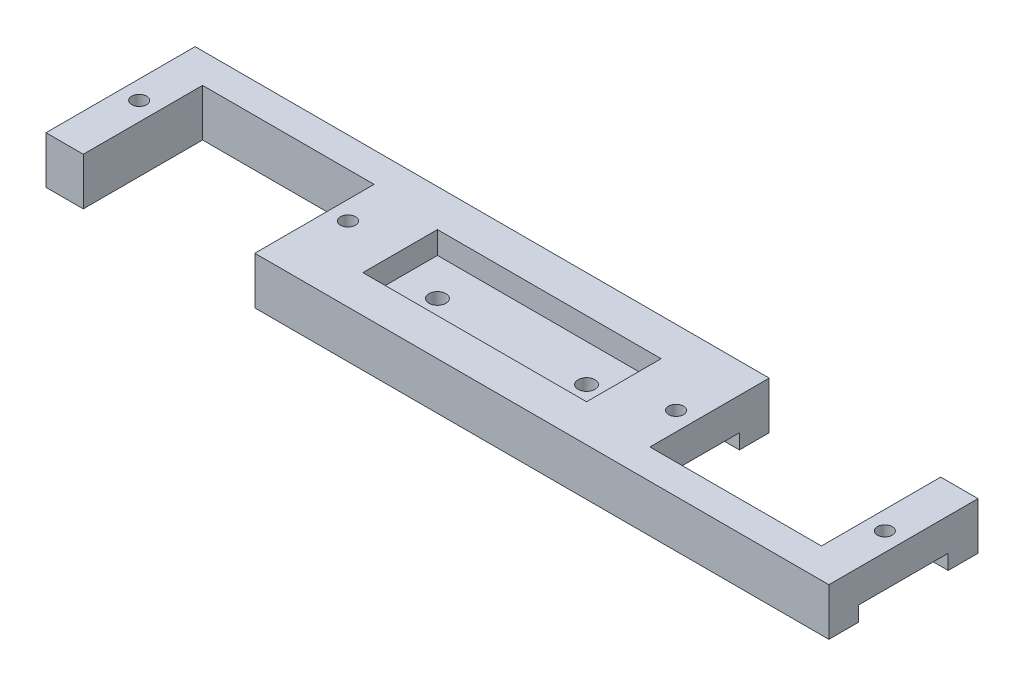
SolidWorks part; units mm, degrees
material "ABS"
ref_plane "Front" through (0, 0, 0) normal (0, 0, 1) x (1, 0, 0)
ref_plane "Top" through (0, 0, 0) normal (0, 1, 0) x (1, 0, 0)
ref_plane "Right" through (0, 0, 0) normal (1, 0, 0) x (0, 0, -1)
sketch "Sketch1" plane through (0, 0, 0) normal (0, 1, 0) x (1, 0, 0)
  line L1 (-52.5, 10) -> (52.5, 10)
  line L2 (-52.5, 10) -> (-52.5, -10)
  line L3 (-52.5, -10) -> (52.5, -10)
  line L4 (52.5, 10) -> (52.5, -10)
  line L5 (-52.5, 10) -> (52.5, -10) construction
  line L6 (-52.5, -10) -> (52.5, 10) construction
  point P0 (0, 0)
  dimension "D1" = 105
  dimension "D2" = 20
extrude "Boss-Extrude1" add sketch "Sketch1" along normal blind 6.35
sketch "Sketch3" plane through (0, 6.35, 0) normal (0, 1, 0) x (1, 0, 0)
  line L0 (-52.5, -10) -> (52.5, -10) construction
  line L1 (-47.5, -10) -> (-24.5, -10)
  line L2 (-47.5, -10) -> (-47.5, 6)
  line L3 (-47.5, 6) -> (-24.5, 6)
  line L4 (-24.5, -10) -> (-24.5, 6)
  line L5 (-52.5, 10) -> (-52.5, -10) construction
  line L6 (52.5, 10) -> (-52.5, 10) construction
  line L7 (52.5, -10) -> (52.5, 10) construction
  line L8 (24.5, 10) -> (47.5, 10)
  line L9 (24.5, 10) -> (24.5, -6)
  line L10 (24.5, -6) -> (47.5, -6)
  line L11 (47.5, 10) -> (47.5, -6)
  dimension "D1" = 23
  dimension "D2" = 5
  dimension "D3" = 4
  dimension "D4" = 5
  dimension "D5" = 4
extrude "Cut-Extrude1" cut sketch "Sketch3" against normal through all
sketch "Sketch4" plane through (0, 0, 0) normal (0, -1, 0) x (1, 0, 0)
  line L0 (24.5, -10) -> (24.5, 6) construction
  line L1 (24.5, 6) -> (19.5, 6)
  line L2 (24.5, 6) -> (24.5, -6)
  line L3 (24.5, -6) -> (19.5, -6)
  line L4 (19.5, 6) -> (19.5, -6)
  line L5 (47.5, 6) -> (47.5, -10) construction
  line L6 (47.5, 6) -> (52.5, 6)
  line L7 (47.5, 6) -> (47.5, -6)
  line L8 (47.5, -6) -> (52.5, -6)
  line L9 (52.5, 6) -> (52.5, -6)
  line L10 (24.5, -10) -> (52.5, 10) construction
  line L11 (24.5, 0) -> (47.5, 0) construction
  point P18 (38.5, 0)
  dimension "D1" = 5
  dimension "D2" = 12
extrude "Cut-Extrude2" cut sketch "Sketch4" against normal blind 2
hole_wizard "M2 Clearance Hole1" positions "Sketch7" profile "Sketch8" hole size "M2" standard "ANSI Metric" end condition through all
sketch "Sketch7" plane through (0, 6.35, 0) normal (0, 1, 0) x (1, 0, 0)
  line L0 (-52.5, 0) -> (52.5, 0) construction
  line L1 (-52.5, 10) -> (-52.5, -10) construction
  line L2 (52.5, -10) -> (52.5, 10) construction
  line L3 (24.5, 10) -> (24.5, -6) construction
  line L4 (47.5, -6) -> (47.5, 10) construction
  line L5 (-47.5, 6) -> (-47.5, -10) construction
  line L6 (-24.5, -10) -> (-24.5, 6) construction
  point P9 (-50, 0)
  point P11 (-22, 0)
  point P13 (22, 0)
  point P15 (50, 0)
  dimension "D1" = 2.5
  dimension "D2" = 2.5
  dimension "D3" = 2.5
  dimension "D4" = 2.5
sketch "Sketch8" plane through (50, 6.35, 0) normal (1, 0, 0) x (0, 0, 1)
  line L0 (0, 0) -> (0, 6.35)
  line L1 (0, 6.35) -> (1, 6.35)
  line L2 (1, 6.35) -> (1, 0)
  line L5 (1, 0) -> (0, 0)
  line L11 (0, -6.35) -> (0, 107.95) construction
  dimension "Thru Hole Dia." = 2
  dimension "Thru Hole Depth" = 6.35
sketch "Sketch9" plane through (0, 6.35, 0) normal (0, 1, 0) x (1, 0, 0)
  line L1 (-15, 5) -> (15, 5)
  line L2 (-15, 5) -> (-15, -5)
  line L3 (-15, -5) -> (15, -5)
  line L4 (15, 5) -> (15, -5)
  line L5 (-15, 5) -> (15, -5) construction
  line L6 (-15, -5) -> (15, 5) construction
  point P0 (0, 0)
  dimension "D1" = 10
  dimension "D2" = 30
extrude "Cut-Extrude3" cut sketch "Sketch9" against normal blind 3
hole_wizard "#2 Clearance Hole1" positions "Sketch12" profile "Sketch14" hole size "#2" standard "ANSI Inch" end condition through all
sketch "Sketch12" plane through (0, 3.35, 0) normal (0, 1, 0) x (1, 0, 0)
  line L0 (-10, 0) -> (10, 0) construction
  point P0 (-10, 0)
  point P2 (10, 0)
  dimension "D1" = 20
sketch "Sketch14" plane through (-10, 3.35, 0) normal (1, 0, 0) x (0, 0, 1)
  line L0 (0, 0) -> (0, 3.35)
  line L1 (0, 3.35) -> (2.032, 3.35)
  line L2 (1.1303, 2.366) -> (1.1303, 0)
  line L5 (1.1303, 0) -> (0, 0)
  line L7 (2.032, 3.35) -> (1.1303, 2.366)
  line L8 (-2.032, 3.35) -> (-1.1303, 2.366) construction
  line L11 (0, -6.35) -> (0, 107.95) construction
  dimension "Thru Hole Dia." = 2.2606
  dimension "Thru Hole Depth" = 3.35
  dimension "Far C'Sink Dia." = 4.064
  dimension "Far C'Sink Angle" = 85
move or copy body "Body-Move/Copy1" [suppressed] bodies to move or copy 106
